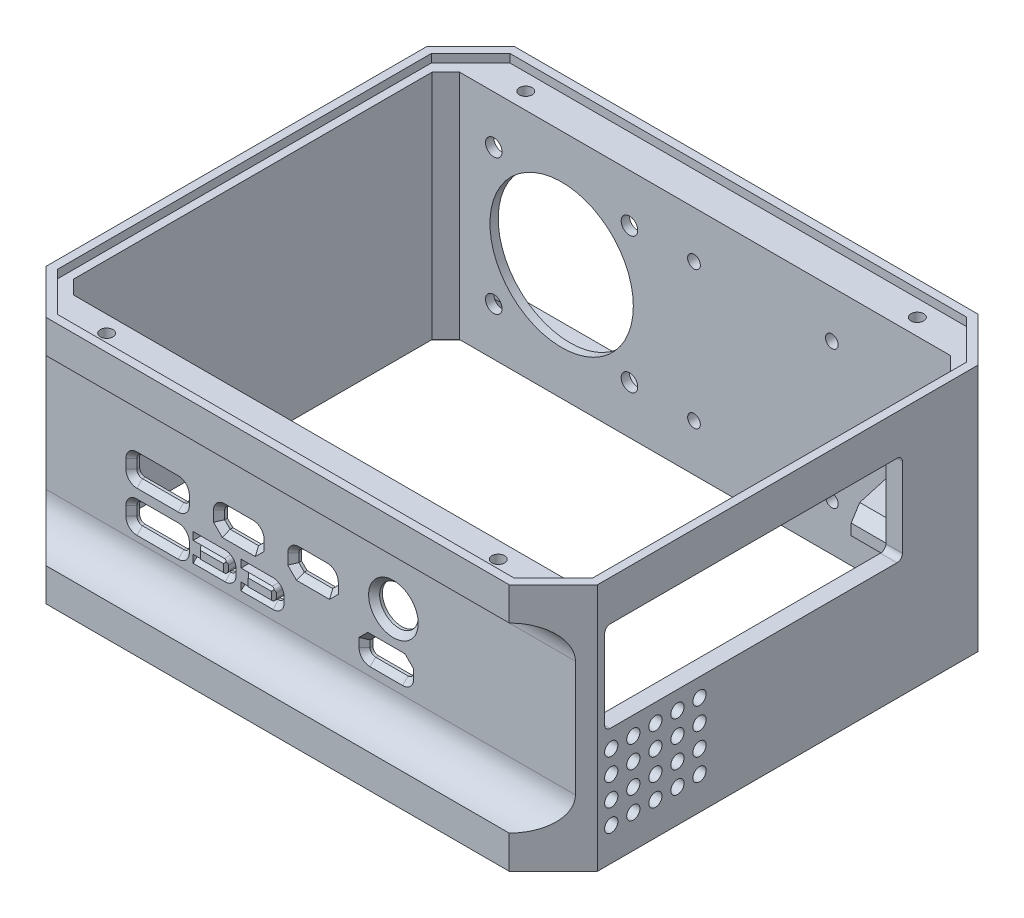
SolidWorks part; units mm, degrees
ref_plane "前视基准面" through (0, 0, 0) normal (0, 0, 1) x (1, 0, 0)
ref_plane "上视基准面" through (0, 0, 0) normal (0, 1, 0) x (1, 0, 0)
ref_plane "右视基准面" through (0, 0, 0) normal (1, 0, 0) x (0, 0, -1)
sketch "草图1" plane through (0, 0, 0) normal (0, 1, 0) x (1, 0, 0)
  line L1 (-34.2475, 38.3062) -> (65.7525, 38.3062)
  line L2 (-34.2475, 38.3062) -> (-34.2475, -46.6938)
  line L3 (-34.2475, -46.6938) -> (65.7525, -46.6938)
  line L4 (65.7525, 38.3062) -> (65.7525, -46.6938)
  dimension "D1" = 100
  dimension "D2" = 85
extrude "凸台-拉伸1" add sketch "草图1" along normal blind 42
chamfer "倒角1" distance 8 angle 45 4 edges at (-34.2475, 21, -38.3062) (-34.2475, 21, 46.6938) (65.7525, 21, -38.3062) (65.7525, 21, 46.6938)
sketch "草图2" plane through (0, 0, 0) normal (0, -1, 0) x (1, 0, 0)
  line L0 (-28.7475, 39.1938) -> (60.2525, 39.1938)
  line L1 (60.2525, 39.1938) -> (62.7525, 36.6938)
  line L2 (62.7525, 36.6938) -> (62.7525, -28.3062)
  line L3 (62.7525, -28.3062) -> (60.2525, -30.8062)
  line L4 (60.2525, -30.8062) -> (-28.7475, -30.8062)
  line L5 (-28.7475, -30.8062) -> (-31.2475, -28.3062)
  line L6 (-31.2475, -28.3062) -> (-31.2475, 36.6938)
  line L7 (-31.2475, 36.6938) -> (-28.7475, 39.1938)
  line L8 (-26.2475, 46.6938) -> (57.7525, 46.6938) construction
  line L9 (-34.2475, -30.3062) -> (-34.2475, 38.6938) construction
  line L10 (57.7525, -38.3062) -> (-26.2475, -38.3062) construction
  line L12 (65.7525, 38.6938) -> (65.7525, -30.3062) construction
  line L13 (65.7525, 38.6938) -> (57.7525, 46.6938) construction
  line L14 (-26.2475, 46.6938) -> (-34.2475, 38.6938) construction
  line L15 (-34.2475, -30.3062) -> (-26.2475, -38.3062) construction
  line L16 (57.7525, -38.3062) -> (65.7525, -30.3062) construction
  dimension "D1" = 7.5
  dimension "D2" = 3
  dimension "D3" = 7.5
  dimension "D4" = 3
  dimension "D5" = 10
  dimension "D6" = 10
extrude "切除-拉伸1" cut sketch "草图2" against normal through all
sketch "草图3" plane through (0, 0, 0) normal (0, -1, 0) x (1, 0, 0)
  line L0 (-34.2475, -30.3062) -> (-26.2475, -38.3062) construction
  line L1 (57.7525, -38.3062) -> (-26.2475, -38.3062) construction
  line L2 (57.7525, -38.3062) -> (65.7525, -30.3062) construction
  line L3 (65.7525, 38.6938) -> (65.7525, -30.3062) construction
  line L4 (65.7525, 38.6938) -> (57.7525, 46.6938) construction
  line L5 (-26.2475, 46.6938) -> (57.7525, 46.6938) construction
  line L6 (-34.2475, -30.3062) -> (-34.2475, 38.6938) construction
  line L7 (-26.2475, 46.6938) -> (-34.2475, 38.6938) construction
  line L8 (-34.2475, -30.3062) -> (-26.2475, -38.3062)
  line L9 (57.7525, -38.3062) -> (-26.2475, -38.3062)
  line L10 (57.7525, -38.3062) -> (65.7525, -30.3062)
  line L11 (65.7525, 38.6938) -> (65.7525, -30.3062)
  line L12 (65.7525, 38.6938) -> (57.7525, 46.6938)
  line L13 (-26.2475, 46.6938) -> (57.7525, 46.6938)
  line L14 (-34.2475, -30.3062) -> (-34.2475, 38.6938)
  line L15 (-26.2475, 46.6938) -> (-34.2475, 38.6938)
  line L16 (-32.7475, -29.6849) -> (-25.6262, -36.8062)
  line L17 (57.1312, -36.8062) -> (-25.6262, -36.8062)
  line L18 (57.1312, -36.8062) -> (64.2525, -29.6849)
  line L19 (64.2525, 38.0725) -> (64.2525, -29.6849)
  line L20 (64.2525, 38.0725) -> (57.1312, 45.1938)
  line L21 (-25.6262, 45.1938) -> (57.1312, 45.1938)
  line L22 (-25.6262, 45.1938) -> (-32.7475, 38.0725)
  line L23 (-32.7475, -29.6849) -> (-32.7475, 38.0725)
  dimension "D1" = 1.5
extrude "凸台-拉伸2" add sketch "草图3" along normal blind 1.5
sketch "草图4" plane through (0, 42, 0) normal (0, 1, 0) x (1, 0, 0)
  line L8 (-25.6262, 36.8062) -> (-32.7475, 29.6849)
  line L9 (57.1312, 36.8062) -> (-25.6262, 36.8062)
  line L10 (64.2525, 29.6849) -> (57.1312, 36.8062)
  line L11 (64.2525, -38.0725) -> (64.2525, 29.6849)
  line L12 (57.1312, -45.1938) -> (64.2525, -38.0725)
  line L13 (-25.6262, -45.1938) -> (57.1312, -45.1938)
  line L14 (-32.7475, -38.0725) -> (-25.6262, -45.1938)
  line L15 (-32.7475, 29.6849) -> (-32.7475, -38.0725)
  line L16 (-25.6262, 36.8062) -> (-32.7475, 29.6849)
  line L17 (57.1312, 36.8062) -> (-25.6262, 36.8062)
  line L18 (64.2525, 29.6849) -> (57.1312, 36.8062)
  line L19 (64.2525, -38.0725) -> (64.2525, 29.6849)
  line L20 (57.1312, -45.1938) -> (64.2525, -38.0725)
  line L21 (-25.6262, -45.1938) -> (57.1312, -45.1938)
  line L22 (-32.7475, -38.0725) -> (-25.6262, -45.1938)
  line L23 (-32.7475, 29.6849) -> (-32.7475, -38.0725)
  line L24 (-26.2475, 38.3062) -> (-34.2475, 30.3062)
  line L25 (57.7525, 38.3062) -> (-26.2475, 38.3062)
  line L26 (65.7525, 30.3062) -> (57.7525, 38.3062)
  line L27 (65.7525, -38.6938) -> (65.7525, 30.3062)
  line L28 (57.7525, -46.6938) -> (65.7525, -38.6938)
  line L29 (-26.2475, -46.6938) -> (57.7525, -46.6938)
  line L30 (-34.2475, -38.6938) -> (-26.2475, -46.6938)
  line L31 (-34.2475, 30.3062) -> (-34.2475, -38.6938)
  line L32 (-26.2475, 38.3062) -> (-34.2475, 30.3062)
  line L33 (57.7525, 38.3062) -> (-26.2475, 38.3062)
  line L34 (65.7525, 30.3062) -> (57.7525, 38.3062)
  line L35 (65.7525, -38.6938) -> (65.7525, 30.3062)
  line L36 (57.7525, -46.6938) -> (65.7525, -38.6938)
  line L37 (-26.2475, -46.6938) -> (57.7525, -46.6938)
  line L38 (-34.2475, -38.6938) -> (-26.2475, -46.6938)
  line L39 (-34.2475, 30.3062) -> (-34.2475, -38.6938)
  dimension "D1" = 0
  dimension "D2" = 0
extrude "凸台-拉伸3" add sketch "草图4" along normal blind 1.5
sketch "草图5" plane through (65.7525, 0, 0) normal (1, 0, 0) x (0, 0, -1)
  line L0 (-46.6938, 43.5) -> (-46.6938, -1.5) construction
  line L1 (-46.6938, 37.5) -> (-40.6938, 37.5)
  line L2 (-46.6938, 37.5) -> (-46.6938, 4.5)
  line L3 (-46.6938, 4.5) -> (-40.6938, 4.5)
  line L4 (-40.6938, 37.5) -> (-40.6938, 4.5)
  line L6 (-38.6938, 43.5) -> (-46.6938, 43.5) construction
  line L7 (-46.6938, -1.5) -> (-38.6938, -1.5) construction
  line L8 (-38.6938, 43.5) -> (-38.6938, -1.5) construction
  dimension "D1" = 2
  dimension "D2" = 6
  dimension "D3" = 6
extrude "切除-拉伸2" cut sketch "草图5" against normal through all
sketch "草图7" plane through (65.7525, 0, 0) normal (1, 0, 0) x (0, 0, -1)
  line L0 (38.3062, 43.5) -> (38.3062, -1.5) construction
  line L1 (38.3062, 37.5) -> (32.3062, 37.5)
  line L2 (38.3062, 37.5) -> (38.3062, 4.5)
  line L3 (38.3062, 4.5) -> (32.3062, 4.5)
  line L4 (32.3062, 37.5) -> (32.3062, 4.5)
  line L6 (30.3062, -1.5) -> (30.3062, 43.5) construction
  dimension "D1" = 2
extrude "切除-拉伸3" cut sketch "草图7" against normal through all
fillet "圆角1" radius 6 4 edges at (15.7525, 37.5, -32.3062) (15.7525, 4.5, -32.3062) (15.7525, 37.5, 40.6938) (15.7525, 4.5, 40.6938)
sketch "草图9" plane through (65.7525, 0, 0) normal (1, 0, 0) x (0, 0, -1)
  line L0 (-59.1262, 18.6) -> (48.9885, 18.6) construction
  line L1 (15.6062, 36.2) -> (-36.3938, 36.2)
  line L2 (16.6062, 35.2) -> (16.6062, 20.8)
  line L3 (15.6062, 19.8) -> (-36.3938, 19.8)
  line L4 (-37.3938, 35.2) -> (-37.3938, 20.8)
  line L5 (29.6849, 0) -> (-38.0725, 0) construction
  line L16 (-39.1938, 42) -> (-39.1938, 0) construction
  arc A0 (-36.3938, 19.8) -> (-37.3938, 20.8) centre (-36.3938, 20.8) cw
  arc A1 (16.6062, 20.8) -> (15.6062, 19.8) centre (15.6062, 20.8) cw
  arc A10 (15.6062, 36.2) -> (16.6062, 35.2) centre (15.6062, 35.2) cw
  arc A11 (-36.3938, 36.2) -> (-37.3938, 35.2) centre (-36.3938, 35.2) ccw
  point P6 (0, 0)
  point P7 (0, 0)
  point P8 (0, 0)
  point P9 (0, 0)
  point P11 (0, 0)
  point P20 (-37.3938, 19.8)
  point P46 (16.6062, 36.2)
  point P49 (-37.3938, 36.2)
  dimension "D10" = 1
  dimension "D2" = 54
  dimension "D5" = 16.4
  dimension "D7" = 1.8
  dimension "D11" = 18.6
  dimension "D12" = 1.2
extrude "切除-拉伸5" cut sketch "草图9" against normal up to next
sketch "草图10" plane through (0, 0, 40.6938) normal (0, 0, 1) x (1, 0, 0)
  line L0 (-69.6787, 18.61) -> (100.0936, 18.61) construction
  line L1 (57.1312, 0) -> (-25.6262, 0) construction
  line L2 (65.7525, 43.5) -> (65.7525, -1.5) construction
  line L4 (12.5966, 23.41) -> (19.7525, 23.41)
  line L5 (12.5966, 23.41) -> (12.5966, 19.91)
  line L6 (12.5966, 19.91) -> (19.7525, 19.91)
  line L7 (19.7525, 23.41) -> (19.7525, 19.91)
  line L8 (-0.8592, 23.41) -> (6.2966, 23.41)
  line L9 (-0.8592, 23.41) -> (-0.8592, 19.91)
  line L10 (-0.8592, 19.91) -> (6.2966, 19.91)
  line L11 (6.2966, 23.41) -> (6.2966, 19.91)
  line L12 (-16.7592, 23.61) -> (-7.2592, 23.61)
  line L13 (-16.7592, 23.61) -> (-16.7592, 19.91)
  line L14 (-16.7592, 19.91) -> (-7.2592, 19.91)
  line L15 (-7.2592, 23.61) -> (-7.2592, 19.91)
  line L16 (-16.7592, 16.21) -> (-7.2592, 16.21)
  line L17 (-16.7592, 16.21) -> (-16.7592, 12.51)
  line L18 (-16.7592, 12.51) -> (-7.2592, 12.51)
  line L19 (-7.2592, 16.21) -> (-7.2592, 12.51)
  line L20 (-5.5592, 16.21) -> (1.2408, 16.21)
  line L21 (-5.5592, 16.21) -> (-5.5592, 13.21)
  line L22 (-5.5592, 13.21) -> (1.2408, 13.21)
  line L23 (1.2408, 16.21) -> (1.2408, 13.21)
  line L24 (3.1189, 16.21) -> (9.9189, 16.21)
  line L25 (3.1189, 16.21) -> (3.1189, 13.21)
  line L26 (3.1189, 13.21) -> (9.9189, 13.21)
  line L27 (9.9189, 16.21) -> (9.9189, 13.21)
  line L28 (25.5189, 16.21) -> (33.4189, 16.21)
  line L29 (25.5189, 16.21) -> (25.5189, 13.01)
  line L30 (25.5189, 13.01) -> (33.4189, 13.01)
  line L31 (33.4189, 16.21) -> (33.4189, 13.01)
  circle A0 centre (30.7525, 23.19) radius 3.5
  dimension "D3" = 7
  dimension "D1" = 18.61
  dimension "D2" = 35
  dimension "D4" = 4.58
  dimension "D5" = 11
  dimension "D6" = 6.3
  dimension "D7" = 6.4
  dimension "D8" = 9.5
  dimension "D9" = 1.3
  dimension "D10" = 3.5
  dimension "D11" = 3.7
  dimension "D12" = 2.4
  dimension "D13" = 73.0117
  dimension "D14" = 6.8
  dimension "D15" = 64.5117
  dimension "D16" = 3
  dimension "D17" = 55.8336
  dimension "D18" = 3.2
  dimension "D19" = 7.9
  dimension "D20" = 32.3336
extrude "切除-拉伸8" cut sketch "草图10" against normal up to next
fillet "圆角2" radius 1 14 edges at (-0.8592, 23.41, 39.9438) (6.2966, 23.41, 39.9438) (19.7525, 23.41, 39.9438) (12.5966, 23.41, 39.9438) (33.4189, 13.01, 39.9438) (25.5189, 13.01, 39.9438) (-7.2592, 12.51, 39.9438) (-7.2592, 16.21, 39.9438) (-16.7592, 16.21, 39.9438) (-16.7592, 12.51, 39.9438) (-16.7592, 19.91, 39.9438) (-16.7592, 23.61, 39.9438) (-7.2592, 23.61, 39.9438) (-7.2592, 19.91, 39.9438)
chamfer "倒角2" distance 1 angle 45 6 edges at (33.4189, 16.21, 39.9438) (25.5189, 16.21, 39.9438) (12.5966, 19.91, 39.9438) (19.7525, 19.91, 39.9438) (6.2966, 19.91, 39.9438) (-0.8592, 19.91, 39.9438)
sketch "草图15" plane through (0, 0, 40.6938) normal (0, 0, 1) x (1, 0, 0)
  line L1 (-5.5592, 15.81) -> (0.8408, 15.81)
  line L2 (-5.5592, 15.81) -> (-5.5592, 13.61)
  line L3 (-5.5592, 13.61) -> (0.8408, 13.61)
  line L4 (0.8408, 15.81) -> (0.8408, 13.61)
  line L6 (3.1189, 16.21) -> (3.1189, 13.21) construction
  line L7 (3.1189, 15.81) -> (9.5189, 15.81)
  line L8 (3.1189, 15.81) -> (3.1189, 13.61)
  line L9 (3.1189, 13.61) -> (9.5189, 13.61)
  line L10 (9.5189, 15.81) -> (9.5189, 13.61)
  line L11 (-5.5592, 16.21) -> (-5.5592, 13.21) construction
  line L12 (1.2408, 16.21) -> (-5.5592, 16.21) construction
  line L13 (-5.5592, 13.21) -> (1.2408, 13.21) construction
  line L14 (1.2408, 13.21) -> (1.2408, 16.21) construction
  line L17 (9.9189, 13.21) -> (9.9189, 16.21) construction
  dimension "D1" = 0.4
  dimension "D2" = 0.4
  dimension "D3" = 0.4
  dimension "D6" = 0.4
extrude "凸台-拉伸4" add sketch "草图15" against normal blind 2
sketch "草图17" plane through (0, 0, 40.6938) normal (0, 0, 1) x (1, 0, 0)
  line L0 (-5.5592, 13.61) -> (0.8408, 13.61) construction
  line L1 (0.8408, 15.81) -> (-4.1592, 15.81)
  line L2 (0.8408, 15.81) -> (0.8408, 13.61)
  line L3 (0.8408, 13.61) -> (-4.1592, 13.61)
  line L4 (-4.1592, 15.81) -> (-4.1592, 13.61)
  line L5 (3.1189, 13.61) -> (9.5189, 13.61) construction
  line L6 (9.5189, 15.81) -> (4.5189, 15.81)
  line L7 (9.5189, 15.81) -> (9.5189, 13.61)
  line L8 (9.5189, 13.61) -> (4.5189, 13.61)
  line L9 (4.5189, 15.81) -> (4.5189, 13.61)
  dimension "D1" = 5
extrude "凸台-拉伸5" add sketch "草图17" along normal blind 0.5 draft 39
fillet "圆角3" radius 0.7 4 edges at (0.8408, 13.61, 39.6938) (0.8408, 15.81, 39.6938) (9.5189, 13.61, 39.6938) (9.5189, 15.81, 39.6938)
fillet "圆角4" radius 1 4 edges at (1.2408, 13.21, 39.9438) (1.2408, 16.21, 39.9438) (9.9189, 13.21, 39.9438) (9.9189, 16.21, 39.9438)
chamfer "倒角3" distance 1 angle 45 51 edges at (33.4189, 14.61, 40.6938) (33.126, 13.3029, 40.6938) (29.4689, 13.01, 40.6938) (25.8118, 13.3029, 40.6938) (32.9189, 15.71, 40.6938) (29.4689, 16.21, 40.6938) (26.0189, 15.71, 40.6938) (25.5189, 14.61, 40.6938) (34.2525, 23.19, 40.6938) (19.7525, 21.66, 40.6938) (19.4596, 23.1171, 40.6938) (16.1746, 23.41, 40.6938) (12.8895, 23.1171, 40.6938) (19.2525, 20.41, 40.6938) (16.1746, 19.91, 40.6938) (13.0966, 20.41, 40.6938) (12.5966, 21.66, 40.6938) (6.0189, 16.21, 40.6938) (9.626, 15.9171, 40.6938) (9.9189, 14.71, 40.6938) (9.626, 13.5029, 40.6938) (6.0189, 13.21, 40.6938) (-0.3592, 20.41, 40.6938) (2.7187, 19.91, 40.6938) (5.7966, 20.41, 40.6938) (6.2966, 21.66, 40.6938) (-0.8592, 21.66, 40.6938) (6.0037, 23.1171, 40.6938) (-0.5664, 23.1171, 40.6938) (2.7187, 23.41, 40.6938) (-2.6592, 13.21, 40.6938) (0.9479, 13.5029, 40.6938) (1.2408, 14.71, 40.6938) (0.9479, 15.9171, 40.6938) (-2.6592, 16.21, 40.6938) (-12.0092, 12.51, 40.6938) (-7.5521, 12.8029, 40.6938) (-16.4664, 12.8029, 40.6938) (-7.2592, 14.36, 40.6938) (-16.7592, 14.36, 40.6938) (-7.5521, 15.9171, 40.6938) (-16.4664, 15.9171, 40.6938) (-12.0092, 16.21, 40.6938) (-12.0092, 19.91, 40.6938) (-7.5521, 20.2029, 40.6938) (-16.4664, 20.2029, 40.6938) (-7.2592, 21.76, 40.6938) (-16.7592, 21.76, 40.6938) (-7.5521, 23.3171, 40.6938) (-16.4664, 23.3171, 40.6938) (-12.0092, 23.61, 40.6938)
sketch "草图18" plane through (0, 42, 0) normal (0, 1, 0) x (1, 0, 0)
  line L0 (-19.7475, 18.8593) -> (-19.7475, 43.8593) construction
  line L1 (51.2525, 38.8565) -> (51.2525, 21.1268) construction
  line L2 (57.7525, 38.3062) -> (-26.2475, 38.3062) construction
  line L3 (-26.2475, -46.6938) -> (57.7525, -46.6938) construction
  line L4 (-34.2475, 30.3062) -> (-34.2475, -38.6938) construction
  line L5 (65.7525, -38.6938) -> (65.7525, 30.3062) construction
  circle A0 centre (-19.7475, 33.8062) radius 1.15
  circle A1 centre (51.2525, 33.8062) radius 1.15
  circle A2 centre (-19.7475, -42.1938) radius 1.15
  circle A3 centre (51.2525, -42.1938) radius 1.15
  point P11 (0, 0)
  point P12 (0, 0)
  point P14 (50.8091, -42.2469)
  point P15 (41.2534, -41.2108)
  point P16 (51.4998, -42.2469)
  point P17 (0, 0)
  point P18 (0, 0)
  dimension "D1" = 2.3
  dimension "D2" = 4.5
  dimension "D3" = 4.5
  dimension "D4" = 14.5
  dimension "D5" = 14.5
extrude "切除-拉伸9" cut sketch "草图18" against normal blind 3
sketch "草图19" plane through (0, 0, 0) normal (0, -1, 0) x (1, 0, 0)
  circle A1 centre (51.2525, 42.1938) radius 1.15
  circle A2 centre (51.2525, 42.1938) radius 1.15
  circle A3 centre (-19.7475, 42.1938) radius 1.15
  circle A4 centre (-19.7475, 42.1938) radius 1.15
  circle A5 centre (51.2525, -33.8062) radius 1.15
  circle A6 centre (51.2525, -33.8062) radius 1.15
  circle A7 centre (-19.7475, -33.8062) radius 1.15
  circle A8 centre (-19.7475, -33.8062) radius 1.15
  dimension "D1" = 0
  dimension "D2" = 0
  dimension "D3" = 0
  dimension "D4" = 0
extrude "切除-拉伸10" cut sketch "草图19" against normal blind 3
sketch "草图20" plane through (0, 0, -30.8062) normal (0, 0, 1) x (1, 0, 0)
  line L0 (-30.7179, 21) -> (58.2821, 21) construction
  line L3 (-34.2475, 43.5) -> (-34.2475, -1.5) construction
  line L4 (60.2525, 42) -> (60.2525, 0) construction
  circle A0 centre (-10.2475, 21) radius 13
  point P8 (60.2525, 21)
  dimension "D1" = 26
  dimension "D2" = 24
extrude "切除-拉伸11" cut sketch "草图20" against normal through all
sketch "草图22" plane through (0, 0, -32.3062) normal (0, 0, -1) x (-1, 0, 0)
  line L1 (-4.7525, 37.5) -> (25.2475, 37.5)
  line L2 (-4.7525, 37.5) -> (-4.7525, 4.5)
  line L3 (-4.7525, 4.5) -> (25.2475, 4.5)
  line L4 (25.2475, 37.5) -> (25.2475, 4.5)
  line L5 (-4.7525, 37.5) -> (25.2475, 4.5) construction
  line L6 (-4.7525, 4.5) -> (25.2475, 37.5) construction
  line L8 (26.2475, 37.5) -> (-57.7525, 37.5) construction
  point P0 (10.2475, 21)
  point P5 (10.2475, 21.7987)
  point P6 (23.7275, 37.5)
  point P7 (-26.0897, 31.5)
  point P9 (23.2475, 37.5)
  point P11 (-2.9496, 6.0975)
  point P12 (25.8703, 6.0975)
  point P16 (23.2475, 6.0975)
  dimension "D1" = 30
extrude "切除-拉伸12" cut sketch "草图22" along normal through all
sketch "草图23" plane through (0, 0, -32.3062) normal (0, 0, -1) x (-1, 0, 0)
  circle A0 centre (-2.0525, 33.3) radius 1.5
  circle A1 centre (22.5475, 33.3) radius 1.5
  circle A2 centre (-2.0525, 8.7) radius 1.5
  circle A3 centre (22.5475, 8.7) radius 1.5
  dimension "D1" = 3
extrude "切除-拉伸13" cut sketch "草图23" against normal up to next
ref_plane "基准面1" through (0, 19.2, 0) normal (0, -1, 0) x (-1, 0, 0)
sketch "草图24" plane through (0, 19.2, 0) normal (0, -1, 0) x (-1, 0, 0)
  line L0 (-62.7525, 17.3062) -> (-55.7525, 17.3062)
  line L1 (-55.7525, 17.3062) -> (-52.7525, 30.8062)
  line L2 (26.2475, 38.3062) -> (-57.7525, 38.3062) construction
  line L3 (-65.7525, 30.3062) -> (-65.7525, -38.6938) construction
  line L5 (28.7475, 30.8062) -> (-60.2525, 30.8062) construction
  line L6 (-62.7525, 28.3062) -> (-62.7525, -36.6938) construction
  line L7 (-52.7525, 30.8062) -> (-60.2525, 30.8062)
  line L8 (-60.2525, 30.8062) -> (-62.7525, 28.3062)
  line L9 (-62.7525, 28.3062) -> (-62.7525, 17.3062)
  dimension "D1" = 21
  dimension "D2" = 13
  dimension "D3" = 10
extrude "凸台-拉伸6" add sketch "草图24" along normal blind 3 and the other way blind 3
chamfer "倒角5" distance 2 angle 45 2 edges at (59.2525, 22.2, -17.3062) (59.2525, 16.2, -17.3062)
sketch "草图25" plane through (0, 0, -30.8062) normal (0, 0, 1) x (1, 0, 0)
  line L0 (82.7668, 21) -> (36.8049, 21) construction
  line L1 (65.7525, -1.5) -> (65.7525, 43.5) construction
  line L2 (41.2525, 36) -> (11.2525, 36) construction
  line L3 (41.2525, 36) -> (41.2525, 6) construction
  line L4 (41.2525, 6) -> (11.2525, 6) construction
  line L5 (11.2525, 36) -> (11.2525, 6) construction
  line L6 (41.2525, 36) -> (11.2525, 6) construction
  line L7 (41.2525, 6) -> (11.2525, 36) construction
  line L8 (60.2525, 42) -> (60.2525, 22.2) construction
  circle A0 centre (13.7525, 33.5) radius 1.15
  circle A1 centre (38.7525, 33.5) radius 1.15
  circle A2 centre (13.7525, 8.5) radius 1.15
  circle A3 centre (38.7525, 8.5) radius 1.15
  point P1 (26.2525, 21)
  point P10 (65.7525, 21)
  point P20 (0, 0)
  point P21 (0, 0)
  point P22 (0, 0)
  dimension "D4" = 2.3
  dimension "D1" = 30
  dimension "D2" = 30
  dimension "D3" = 34
  dimension "D5" = 2.5
extrude "切除-拉伸14" cut sketch "草图25" against normal up to next
sketch "草图26" plane through (65.7525, 0, 0) normal (1, 0, 0) x (0, 0, -1)
  line L2 (-38.6938, 43.5) -> (-38.6938, -1.5) construction
  line L3 (30.3062, -1.5) -> (-38.6938, -1.5) construction
  circle A0 centre (-36.1938, 4.5) radius 1.2
  circle A1 centre (-32.1938, 4.5) radius 1.2
  circle A2 centre (-28.1938, 4.5) radius 1.2
  circle A3 centre (-24.1938, 4.5) radius 1.2
  circle A4 centre (-20.1938, 4.5) radius 1.2
  circle A5 centre (-32.1938, 8.5) radius 1.2
  circle A6 centre (-28.1938, 8.5) radius 1.2
  circle A7 centre (-24.1938, 8.5) radius 1.2
  circle A8 centre (-20.1938, 8.5) radius 1.2
  circle A9 centre (-32.1938, 12.5) radius 1.2
  circle A10 centre (-28.1938, 12.5) radius 1.2
  circle A11 centre (-24.1938, 12.5) radius 1.2
  circle A12 centre (-20.1938, 12.5) radius 1.2
  circle A13 centre (-32.1938, 16.5) radius 1.2
  circle A14 centre (-28.1938, 16.5) radius 1.2
  circle A15 centre (-24.1938, 16.5) radius 1.2
  circle A16 centre (-20.1938, 16.5) radius 1.2
  circle A17 centre (-36.1938, 8.5) radius 1.2
  circle A18 centre (-36.1938, 12.5) radius 1.2
  circle A19 centre (-36.1938, 16.5) radius 1.2
  dimension "D3" = 2.4
  dimension "D1" = 2.5
  dimension "D2" = 6
  dimension "D4" = 5
  dimension "D5" = 4
extrude "切除-拉伸15" cut sketch "草图26" against normal up to next
